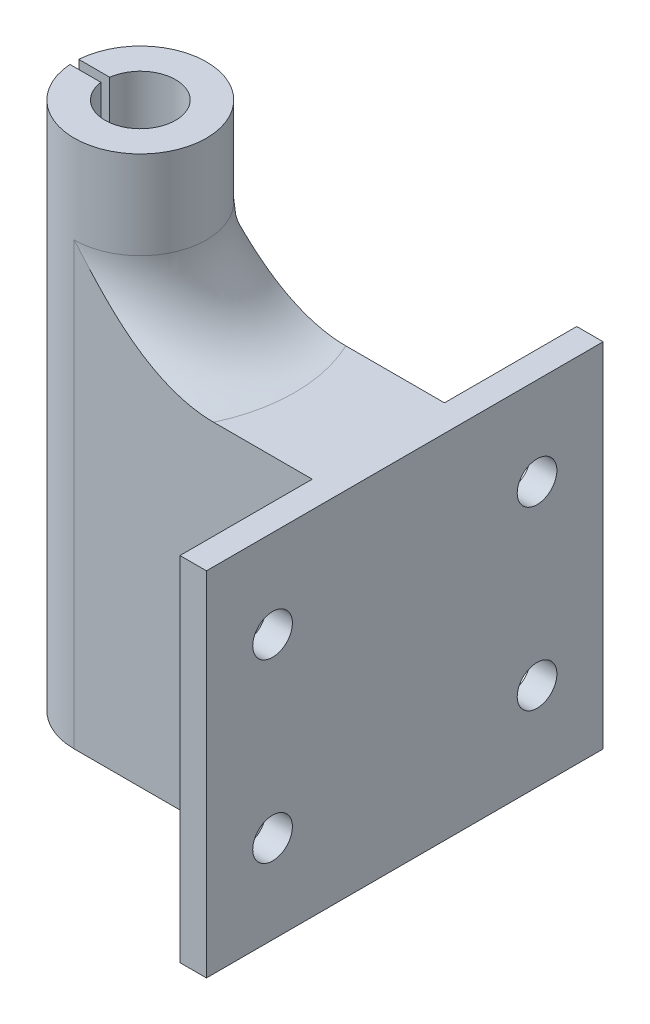
SolidWorks part; units mm, degrees
ref_plane "Front Plane" through (0, 0, 0) normal (0, 0, 1) x (1, 0, 0)
ref_plane "Top Plane" through (0, 0, 0) normal (0, 1, 0) x (1, 0, 0)
ref_plane "Right Plane" through (0, 0, 0) normal (1, 0, 0) x (0, 0, -1)
sketch "Sketch1" plane through (0, 0, 0) normal (0, 0, 1) x (1, 0, 0)
  line L0 (0, 0) -> (0, 37)
  line L1 (0, 37) -> (19, 37)
  line L2 (19, 37) -> (19, 40)
  line L3 (19, 40) -> (-37.5, 40)
  line L4 (-37.5, 40) -> (-37.5, 0)
  line L5 (-37.5, 0) -> (0, 0)
  dimension "D1" = 37
  dimension "D2" = 19
  dimension "D3" = 37.5
  dimension "D4" = 3
extrude "Boss-Extrude1" add sketch "Sketch1" along normal blind 15
sketch "Sketch2" plane through (0, 40, 0) normal (0, 1, 0) x (1, 0, 0)
  line L0 (-37.5, -7.5) -> (-30, -7.5) construction
  line L1 (-37.5, -15) -> (-37.5, 0) construction
  line L4 (-33.9686, -7) -> (-37.5, -7)
  line L5 (-37.5, -7) -> (-37.5, -8)
  line L6 (-37.5, -8) -> (-33.9686, -8)
  arc A0 (-33.9686, -8) -> (-33.9686, -7) centre (-30, -7.5) ccw
  dimension "D1" = 8
  dimension "D2" = 7.5
  dimension "D3" = 1
  dimension "D4" = 0.5
extrude "Cut-Extrude1" cut sketch "Sketch2" against normal blind 20
fillet "Fillet1" radius 7.5 2 edges at (-37.5, 20, 0) (-37.5, 20, 15)
sketch "Sketch3" plane through (0, 0, 15) normal (0, 0, 1) x (1, 0, 0)
  line L0 (19, 37) -> (0, 37)
  line L1 (0, 37) -> (0, 0)
  line L2 (0, 0) -> (-3, 0)
  line L3 (-30, 0) -> (0, 0) construction
  line L4 (-3, 0) -> (-3, 40)
  line L5 (19, 40) -> (-30, 40) construction
  line L6 (-3, 40) -> (19, 40)
  line L7 (19, 40) -> (19, 37)
  dimension "D1" = 3
extrude "Boss-Extrude2" add sketch "Sketch3" along normal blind 15
sketch "Sketch4" plane through (0, 0, 0) normal (0, 0, -1) x (-1, 0, 0)
  line L0 (-19, 40) -> (3, 40)
  line L1 (-19, 40) -> (30, 40) construction
  line L2 (3, 40) -> (3, 0)
  line L3 (30, 0) -> (0, 0) construction
  line L4 (3, 0) -> (0, 0)
  line L5 (0, 0) -> (0, 37)
  line L6 (0, 37) -> (-19, 37)
  line L7 (-19, 37) -> (-19, 40)
  dimension "D1" = 3
extrude "Boss-Extrude3" add sketch "Sketch4" along normal blind 15
sketch "Sketch5" plane through (-3, 0, 0) normal (-1, 0, 0) x (0, 0, 1)
  line L0 (-7.5, 40) -> (-7.5, 0) construction
  line L1 (-15, 40) -> (0, 40) construction
  line L2 (-15, 0) -> (0, 0) construction
  circle A0 centre (-7.5, 30) radius 2.25
  circle A1 centre (-7.5, 10) radius 2.25
  dimension "D1" = 4.5
  dimension "D2" = 4.5
  dimension "D3" = 10
  dimension "D4" = 10
extrude "Cut-Extrude2" cut sketch "Sketch5" against normal blind 15
ref_plane "Plane1" through (0, 0, 7.5) normal (0, 0, 1) x (1, 0, 0)
mirror "Mirror1" about plane through (0, 0, 7.5) normal (0, 0, 1) of "Cut-Extrude2"
sketch "Sketch6" plane through (0, 0, -15) normal (0, 0, -1) x (-1, 0, 0)
  line L1 (0, 37) -> (-26.056, 37)
  line L2 (0, 37) -> (0, 67.2435)
  line L3 (0, 67.2435) -> (-26.056, 67.2435)
  line L4 (-26.056, 37) -> (-26.056, 67.2435)
extrude "Cut-Extrude3" cut sketch "Sketch6" against normal through all both and the other way through all
sketch "Sketch7" plane through (0, 40, 0) normal (0, 1, 0) x (1, 0, 0)
  line L9 (-3, -30) -> (0, -30)
  line L10 (0, -30) -> (0, 15)
  line L11 (0, 15) -> (-3, 15)
  line L12 (-3, 15) -> (-3, 0)
  line L13 (-3, 0) -> (-30, 0)
  line L14 (-37.4833, -7) -> (-33.9686, -7)
  line L15 (-33.9686, -8) -> (-37.4833, -8)
  line L16 (-30, -15) -> (-3, -15)
  line L17 (-3, -15) -> (-3, -30)
  line L23 (-37.4833, -7) -> (-33.9686, -7)
  line L24 (-33.9686, -8) -> (-37.4833, -8)
  arc A0 (-30, 0) -> (-30, -15) centre (-30, -7.5) cw
  arc A3 (-30, 0) -> (-37.4833, -7) centre (-30, -7.5) ccw
  arc A4 (-33.9686, -8) -> (-33.9686, -7) centre (-30, -7.5) ccw
  arc A5 (-37.4833, -8) -> (-30, -15) centre (-30, -7.5) ccw
  arc A6 (-30, 0) -> (-37.4833, -7) centre (-30, -7.5) ccw
  arc A7 (-33.9686, -8) -> (-33.9686, -7) centre (-30, -7.5) ccw
  arc A8 (-37.4833, -8) -> (-30, -15) centre (-30, -7.5) ccw
  dimension "D1" = 0
extrude "Boss-Extrude4" add sketch "Sketch7" along normal blind 20
fillet "Fillet2" radius 10 1 edges at (-22.5, 40, 7.5)
